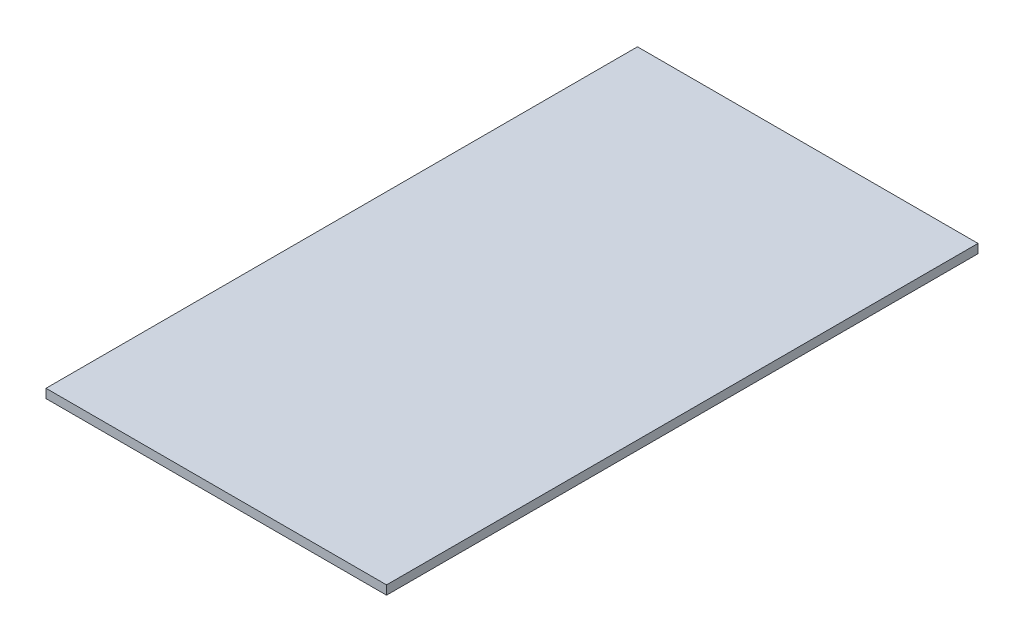
SolidWorks part; units mm, degrees
ref_plane "Front Plane" through (0, 0, 0) normal (0, 0, 1) x (1, 0, 0)
ref_plane "Top Plane" through (0, 0, 0) normal (0, 1, 0) x (1, 0, 0)
ref_plane "Right Plane" through (0, 0, 0) normal (1, 0, 0) x (0, 0, -1)
sketch "Sketch1" plane through (0, 0, 0) normal (0, 1, 0) x (1, 0, 0)
  line L1 (0, 0) -> (38, 0)
  line L2 (0, 0) -> (0, 66)
  line L3 (0, 66) -> (38, 66)
  line L4 (38, 0) -> (38, 66)
  dimension "D1" = 38
  dimension "D2" = 66
extrude "Boss-Extrude1" add sketch "Sketch1" along normal blind 1
